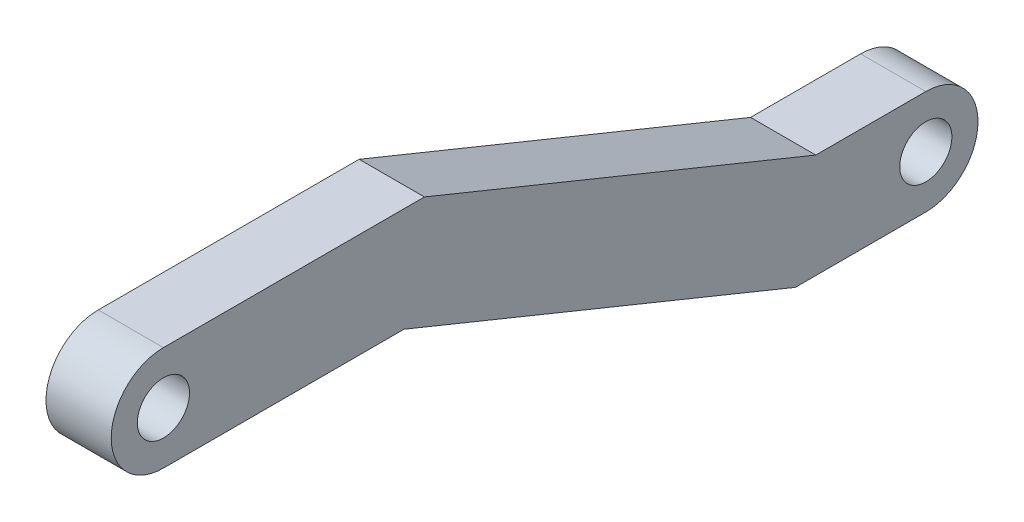
SolidWorks part; units mm, degrees
ref_plane "Front Plane" through (0, 0, 0) normal (0, 0, 1) x (1, 0, 0)
ref_plane "Top Plane" through (0, 0, 0) normal (0, 1, 0) x (1, 0, 0)
ref_plane "Right Plane" through (0, 0, 0) normal (1, 0, 0) x (0, 0, -1)
sketch "Sketch1" plane through (0, 0, 0) normal (1, 0, 0) x (0, 0, -1)
  line L4 (-16.09, -2) -> (16.09, -2)
  line L6 (-16.09, 2) -> (16.09, 2)
  line L8 (-16.09, -2) -> (16.09, 2) construction
  line L9 (-16.09, 2) -> (16.09, -2) construction
  arc A4 (16.09, 2) -> (16.09, -2) centre (16.09, 0) cw
  arc A5 (-16.09, 2) -> (-16.09, -2) centre (-16.09, 0) ccw
  circle A6 centre (-16.09, 0) radius 1
  circle A7 centre (16.09, 0) radius 1
  point P0 (0, 0)
  point P1 (0, 0)
  dimension "D2" = 4
  dimension "D3" = 2
  dimension "D1" = 32.18
sketch "Sketch2" plane through (0, 0, 0) normal (1, 0, 0) x (0, 0, -1)
  line L19 (-10.0015, -2) -> (19.2167, -8.1093) construction
  line L20 (15, -6.1093) -> (19.2167, -6.1093)
  line L21 (15, -6.1093) -> (0, 0)
  line L22 (0, 0) -> (-10.0015, 0)
  line L23 (14.2167, -10.1093) -> (19.2167, -10.1093)
  line L24 (14.2167, -10.1093) -> (-0.7833, -4)
  line L25 (-0.7833, -4) -> (-10.0015, -4)
  arc A6 (19.2167, -6.1093) -> (19.2167, -10.1093) centre (19.2167, -8.1093) cw
  arc A7 (-10.0015, 0) -> (-10.0015, -4) centre (-10.0015, -2) ccw
  circle A8 centre (-10.0015, -2) radius 1
  circle A9 centre (19.2167, -8.1093) radius 1
  point P0 (11.5434, -10.4481)
  point P1 (11.3115, -4.224)
  point P13 (-19.7285, 3.6014)
  point P14 (-20.1998, 4.224)
  dimension "D1" = 4
  dimension "D5" = 2
  dimension "D7" = 11.81
  dimension "D8" = 20
  dimension "D4" = 4
  dimension "D2" = 29.85
  dimension "D3" = 4
  dimension "D6" = 5
extrude "Boss-Extrude1" add sketch "Sketch2" along normal blind 2.5
